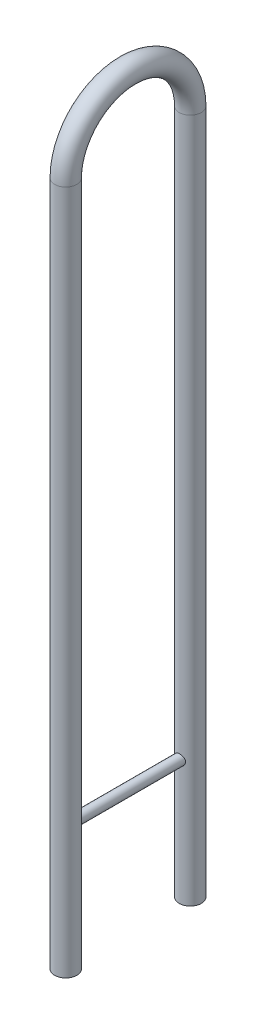
SolidWorks part; units mm, degrees
ref_plane "Front Plane" through (0, 0, 0) normal (1, 0, 0) x (0, 1, 0)
ref_plane "Top Plane" through (0, 0, 0) normal (0, 0, 1) x (0, 1, 0)
ref_plane "Right Plane" through (0, 0, 0) normal (0, 1, 0) x (-1, 0, 0)
sketch "Sketch2" plane through (0, 0, 0) normal (1, 0, 0) x (0, 1, 0)
  line L0 (0, 76.2) -> (-838.2, 76.2)
  line L1 (0, -76.2) -> (-838.2, -76.2)
  line L2 (-685.8, 76.2) -> (-685.8, -76.2)
  arc A0 (0, 76.2) -> (0, -76.2) centre (0, 0) cw
  point P8 (0, 0)
  dimension "D1" = 76.2
  dimension "D2" = 838.2
  dimension "D3" = 152.4
sweep "Sweep1" add path "Sketch2" circular profile diameter 27.178 parameters "D3"=27.178
sweep "Sweep2" add path "Sketch2<3>" circular profile diameter 12.7 parameters "D3"=12.7
sketch "Sketch2<3>" plane through (0, 0, 0) normal (1, 0, 0) x (0, 1, 0) same geometry as "Sketch2"
shell "Shell1" thickness 1.524 removed face at (0, -838.2, -89.789) removed face at (0, -838.2, 89.789)
